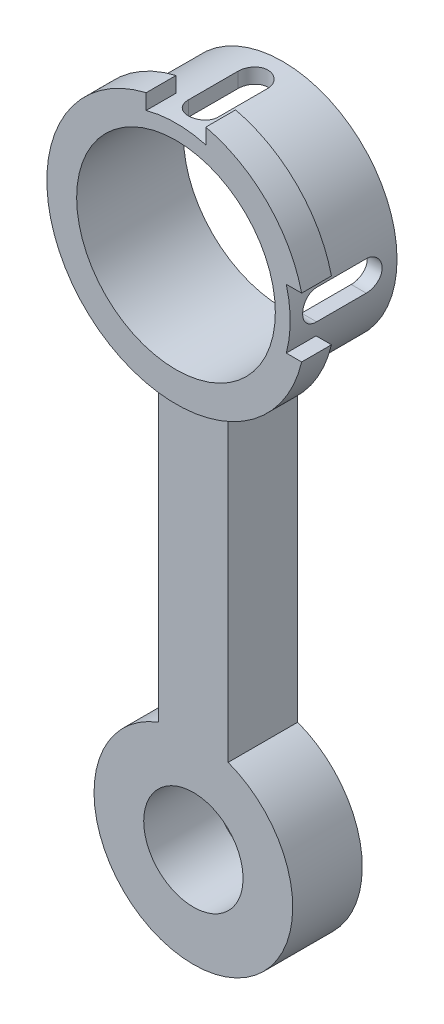
SolidWorks part; units mm, degrees
ref_plane "Alzado" through (0, 0, 0) normal (0, 0, 1) x (1, 0, 0)
ref_plane "Planta" through (0, 0, 0) normal (0, 1, 0) x (1, 0, 0)
ref_plane "Vista lateral" through (0, 0, 0) normal (1, 0, 0) x (0, 0, -1)
sketch "Croquis1" plane through (0, 0, 0) normal (0, 0, 1) x (1, 0, 0)
  circle A0 centre (0, 0) radius 10
  dimension "D1" = 20
extrude "Saliente-Extruir1" add sketch "Croquis1" along normal blind 3
sketch "Croquis2" plane through (0, 0, 3) normal (0, 0, 1) x (1, 0, 0)
  circle A0 centre (0, 0) radius 2.5
  circle A1 centre (0, 0) radius 4
  circle A2 centre (0, 0) radius 11.5
  circle A3 centre (0, 0) radius 10
  circle M1 centre (0, 0) radius 10
  dimension "D1" = 5
  dimension "D2" = 8
  dimension "D3" = 23
extrude "Saliente-Extruir3" add sketch "Croquis2" along normal blind 8 separate body contours A2 M1 region at (-11.1747, 0, 3)
sketch "Croquis3" plane through (0, 0, 3) normal (0, 0, -1) x (-1, 0, 0)
  circle A0 centre (0, 0) radius 11.5
  circle A1 centre (0, 0) radius 10
extrude "Saliente-Extruir4" add sketch "Croquis3" along normal up to surface (3 mm away) up to face at (10, 0, 0)
ref_plane "Plano1" through (0, 11.5, 0) normal (0, 1, 0) x (1, 0, 0)
sketch "Croquis4" plane through (0, 11.5, 0) normal (0, 1, 0) x (1, 0, 0)
  line L0 (0, -9.5) -> (0, -11) construction
  line L2 (0, -8) -> (0, -3) construction
  line L3 (-1.5, -8) -> (-1.5, -3)
  line L4 (1.5, -8) -> (1.5, -3)
  line L5 (-11.5, -11) -> (11.5, -11) construction
  line L6 (0, -1.5) -> (0, 0) construction
  arc A1 (-1.5, -8) -> (1.5, -8) centre (0, -8) ccw
  arc A2 (1.5, -3) -> (-1.5, -3) centre (0, -3) ccw
  point P0 (0, -5.5)
  dimension "D2" = 1.5
  dimension "D1" = 1.5
  dimension "D3" = 1.5
extrude "Cortar-Extruir1" cut sketch "Croquis4" against normal blind 8
sketch "Croquis7" plane through (0, 0, 11) normal (0, 0, 1) x (1, 0, 0)
  line L0 (0, 11.5) -> (0, 0) construction
  line L1 (6.05, 11.5) -> (-6.05, 11.5) construction
  line L2 (0, 0) -> (11.5, 0) construction
  circle A0 centre (0, 0) radius 11.5 construction
ref_plane "Plano2" through (0, 11.5, 0) normal (0, 1, 0) x (1, 0, 0)
ref_plane "Plano3" through (0, 11.5, 0) normal (0, 1, 0) x (1, 0, 0)
sketch "Croquis9" plane through (0, 0, 11) normal (0, 0, 1) x (1, 0, 0)
  line L0 (11.5, 0) -> (11.5, 3)
  line L1 (11.5, 3) -> (12.0602, 3)
  line L2 (12.0602, 3) -> (12.0602, -3)
  line L3 (11.5, 0) -> (11.5, -3)
  line L4 (12.0602, -3) -> (11.5, -3)
  dimension "D1" = 3
  dimension "D2" = 3
extrude "Saliente-Extruir5" add sketch "Croquis9" against normal blind 8 separate body
sketch "Croquis10" plane through (12.0602, 0, 0) normal (1, 0, 0) x (0, 0, -1)
  line L0 (-11, 3) -> (-11, 0) construction
  line L1 (-11, -3) -> (-11, 3) construction
  line L2 (-3, 0) -> (-8, 0) construction
  line L3 (-3, -3) -> (-3, 3) construction
  line L6 (-3, -1.5) -> (-8, -1.5)
  line L7 (-3, 1.5) -> (-8, 1.5)
  line L8 (-11, 0) -> (-9.5, 0) construction
  line L9 (0, 0) -> (-1.5, 0) construction
  arc A2 (-3, -1.5) -> (-3, 1.5) centre (-3, 0) ccw
  arc A3 (-8, 1.5) -> (-8, -1.5) centre (-8, 0) ccw
  point P7 (-8.5994, 0)
  point P8 (-5.5, 0)
  point P17 (-9.5, 0)
  dimension "D2" = 1.5
  dimension "D3" = 1.5
  dimension "D1" = 1.5
extrude "Cortar-Extruir2" cut sketch "Croquis10" against normal blind 8
sketch "Croquis11" plane through (0, 0, 11) normal (0, 0, 1) x (1, 0, 0)
  line L1 (11.5, 3) -> (12.0602, 3)
  line L2 (11.5, 3) -> (11.5, -3)
  line L3 (11.5, -3) -> (12.0602, -3)
  line L4 (12.0602, 3) -> (12.0602, -3)
extrude "Cortar-Extruir3" cut sketch "Croquis11" against normal blind 8
ref_plane "Plano4" through (-11.5, 0, 0) normal (-1, 0, 0) x (0, 0, 1)
sketch "Croquis12" plane through (0, 0, 3) normal (0, 0, 1) x (1, 0, 0)
  line L0 (0, 0) -> (0, -11.5) construction
  line L1 (0, -11.5) -> (-2.5, -11.5)
  line L2 (0, -11.5) -> (2.5, -11.5)
  line L3 (-2.5, -11.5) -> (-2.5, -10.878)
  line L4 (-2.5, -11.5) -> (2.5, -11.5)
  line L5 (-2.5, -11.5) -> (-2.5, -61.5)
  line L6 (-2.5, -61.5) -> (2.5, -61.5)
  line L7 (2.5, -11.5) -> (2.5, -61.5)
  line L8 (-2.5, -10.878) -> (0, -10.878)
  line L9 (0, -10.878) -> (0, -11.5)
  line L10 (0, -10.878) -> (2.5, -10.878)
  line L11 (2.5, -10.878) -> (2.5, -11.5)
  circle A0 centre (0, 0) radius 11.5 construction
  dimension "D1" = 2.5
  dimension "D2" = 2.5
  dimension "D3" = 50
extrude "Saliente-Extruir6" add sketch "Croquis12" against normal up to surface (3 mm away) contours L9 L8 L3 L1 | L11 L10 L9 L2 | L7 L2 L1 L5 L6 region at (0, -36.5, 3) region at (1.25, -11.189, 3) region at (-1.25, -11.189, 3) up to face at (11.5, 0, 0)
sketch "Croquis13" plane through (0, 0, 3) normal (0, 0, 1) x (1, 0, 0)
  line L1 (-2.5, -11.225) -> (2.5, -11.225)
  line L2 (-2.5, -11.225) -> (-2.5, -61.5)
  line L3 (-2.5, -61.5) -> (2.5, -61.5)
  line L4 (2.5, -11.225) -> (2.5, -61.5)
extrude "Saliente-Extruir7" add sketch "Croquis13" along normal up to surface (8 mm away) up to face at (10, 0, 11)
sketch "Croquis15" plane through (2.5, 0, 0) normal (1, 0, 0) x (0, 0, -1)
  line L0 (0, -11.225) -> (-11, -11.225) construction
  line L1 (-11, -61.5) -> (-9, -61.5)
  line L2 (-11, -61.5) -> (-11, -11.225)
  line L3 (-11, -11.225) -> (-9, -11.225)
  line L4 (-9, -61.5) -> (-9, -11.225)
  line L6 (0, -61.5) -> (-2, -61.5)
  line L7 (0, -61.5) -> (0, -11.225)
  line L8 (0, -11.225) -> (-2, -11.225)
  line L9 (-2, -61.5) -> (-2, -11.225)
  dimension "D1" = 2
  dimension "D2" = 2
extrude "Cortar-Extruir4" cut sketch "Croquis15" against normal blind 8
sketch "Croquis16" plane through (0, 0, 9) normal (0, 0, 1) x (1, 0, 0)
  line L0 (-2.5, -61.5) -> (-3.5, -61.5)
  line L1 (2.5, -61.5) -> (3.5, -61.5)
  line L2 (-3.5, -61.5) -> (-3.5, -10.233)
  line L3 (-3.5, -10.233) -> (3.5, -10.233)
  line L4 (3.5, -10.233) -> (3.5, -61.5)
  line L9 (-2.5, -61.5) -> (2.5, -61.5)
  line L10 (2.5, -61.5) -> (2.5, -11.225)
  line L11 (2.5, -11.225) -> (-2.5, -11.225)
  line L12 (-2.5, -11.225) -> (-2.5, -61.5)
  line L13 (-2.5, -61.5) -> (2.5, -61.5)
  dimension "D1" = 1
  dimension "D2" = 1
  dimension "D3" = 0
extrude "Saliente-Extruir8" add sketch "Croquis16" against normal up to surface (7 mm away) up to face at (0, -36.3625, 2)
sketch "Croquis21" plane through (0, 0, 2) normal (0, 0, -1) x (-1, 0, 0)
  line L0 (0, -11.225) -> (0, -52.725) construction
  line L1 (2.5, -11.225) -> (-2.5, -11.225) construction
  circle A0 centre (0, -52.725) radius 10
  dimension "D2" = 20
  dimension "D1" = 41.5
extrude "Saliente-Extruir9" add sketch "Croquis21" against normal up to surface (7 mm away) up to face at (0, -27.8969, 9)
sketch "Croquis22" plane through (0, 0, 2) normal (0, 0, -1) x (-1, 0, 0)
  circle A0 centre (0, -52.725) radius 5
  dimension "D1" = 10
extrude "Cortar-Extruir5" cut sketch "Croquis22" against normal blind 30
sketch "Croquis23" plane through (0, 0, 11) normal (0, 0, 1) x (1, 0, 0)
  line L0 (-2.5, -11.225) -> (2.5, -11.225) construction
  line L1 (-2.5, -11.225) -> (2.5, -11.225)
  arc A0 (2.5, -11.225) -> (-2.5, -11.225) centre (0, 0) ccw construction
  arc A1 (2.5, -11.225) -> (-2.5, -11.225) centre (0, 0) ccw
  circle A2 centre (0, 0) radius 10 construction
  circle A3 centre (0, 0) radius 10
extrude "Saliente-Extruir10" add sketch "Croquis23" along normal blind 1.25
sketch "Croquis24" plane through (0, 0, 12.25) normal (0, 0, 1) x (1, 0, 0)
  line L0 (-2.5, -11.225) -> (2.5, -11.225) construction
  line L1 (-2.5, -11.225) -> (2.5, -11.225)
  circle A0 centre (0, 0) radius 10 construction
  arc A1 (2.5, -11.225) -> (-2.5, -11.225) centre (0, 0) ccw construction
  circle A2 centre (0, 0) radius 10
  arc A3 (2.5, -11.225) -> (-2.5, -11.225) centre (0, 0) ccw
extrude "Cortar-Extruir6" cut sketch "Croquis24" against normal blind 1.5
sketch "Croquis25" plane through (0, 0, 10.75) normal (0, 0, 1) x (1, 0, 0)
  circle A0 centre (0, 0) radius 13
  arc A1 (2.5, -11.225) -> (-2.5, -11.225) centre (0, 0) ccw construction
  arc A2 (2.5, -11.225) -> (-2.5, -11.225) centre (0, 0) ccw
  arc M2 (2.5, -11.225) -> (-2.5, -11.225) centre (0, 0) ccw
  line M3 (-2.5, -11.225) -> (2.5, -11.225)
  dimension "D1" = 26
  dimension "D2" = 23
extrude "Saliente-Extruir11" add sketch "Croquis25" against normal blind 3 contours A0 M2 M3 region at (-12.6323, 0, 10.75)
sketch "Croquis27" plane through (0, 0, 0) normal (0, 0, -1) x (-1, 0, 0)
  line L1 (6.05, 11.5) -> (-6.05, 11.5) construction
  line L3 (3, 11.5) -> (3, 12.6491)
  line L7 (3, 12.6491) -> (3, 13.5864)
  line L8 (3, 13.5864) -> (-0.0015, 13.5864)
  line L10 (3, 11.5) -> (3, 11.3699)
  line L11 (-3, 11.5) -> (-3, 11.3699)
  line L12 (3, 11.5) -> (-3, 11.5)
  line L13 (-0.0015, 13.5864) -> (-3, 13.5864)
  line L14 (-3, 13.5864) -> (-3, 11.3699)
  line L15 (-3, 11.3699) -> (-3, 11.1018)
  line L16 (3, 11.3699) -> (3, 11.1018)
  arc A0 (3.5, -12.52) -> (-3.5, -12.52) centre (0, 0) ccw construction
  arc A2 (2.5, -11.225) -> (-2.5, -11.225) centre (0, 0) ccw construction
  arc A3 (2.5, -11.225) -> (-2.5, -11.225) centre (0, 0) ccw
  arc M6 (2.5, -11.225) -> (-2.5, -11.225) centre (0, 0) ccw
  dimension "D1" = 3.0015
  dimension "D2" = 3
  dimension "D3" = 3
extrude "Cortar-Extruir10" cut sketch "Croquis27" against normal blind 13 contours L11 L15 L12 M6 | L16 L10 L12 M6 | L13 L14 L12 L3 L7 L8 region at (0, 12.5432, 0) region at (-2.2526, 11.3809, 0) region at (2.2526, 11.3809, 0)
sketch "Croquis28" plane through (0, 0, 0) normal (0, 0, -1) x (-1, 0, 0)
  line L0 (-11.5, 0) -> (-11.5, 3)
  line L1 (-11.5, 0) -> (-11.5, -3)
  line L2 (-11.5, 3) -> (-11.1018, 3)
  line L3 (-11.5, -3) -> (-11.1018, -3)
  line L4 (-11.5, -3) -> (-13.8026, -3)
  line L5 (-13.8026, -3) -> (-13.8026, 3)
  line L6 (-13.8026, 3) -> (-11.5, 3)
  arc A0 (-11.4018, -1.5) -> (-3.5, -10.9545) centre (0, 0) ccw construction
  arc M3 (2.5, -11.225) -> (-2.5, -11.225) centre (0, 0) ccw
  dimension "D1" = 3
  dimension "D2" = 3
extrude "Cortar-Extruir11" cut sketch "Croquis28" against normal blind 13 contours L6 L5 L4 L1 L0 | L2 L0 M3 | L1 L3 M3 region at (12.6513, 0, 0) region at (11.3809, -2.2526, 0) region at (11.3809, 2.2526, 0)
sketch "Croquis30" plane through (0, 0, 3) normal (0, 0, 1) x (1, 0, 0)
  circle A0 centre (0, 0) radius 10
extrude "Cortar-Extruir14" cut sketch "Croquis30" against normal blind 10
